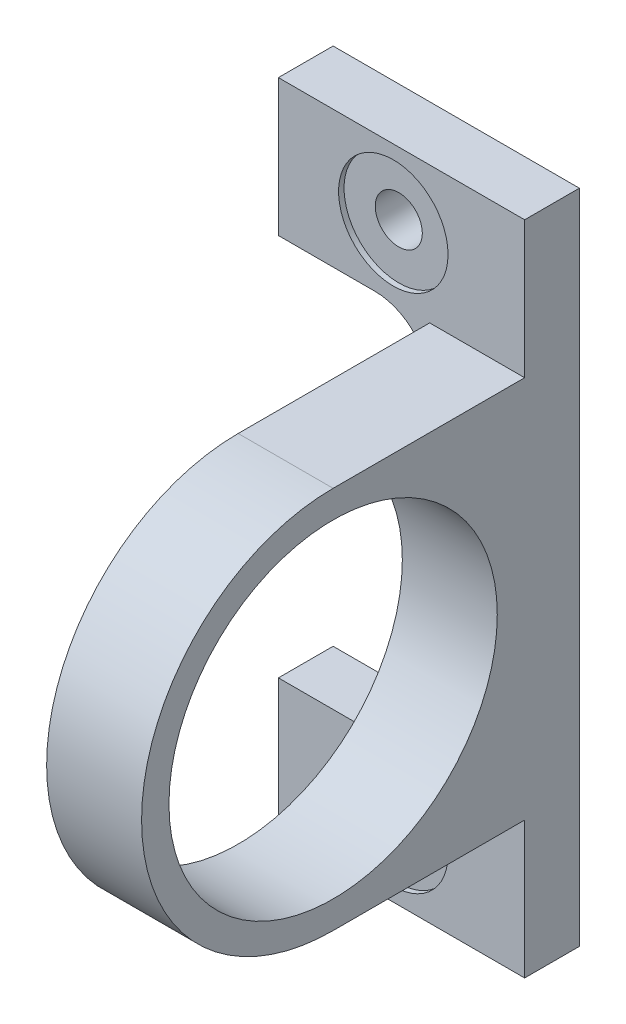
SolidWorks part; units mm, degrees
ref_plane "前视基准面" through (0, 0, 0) normal (0, 0, 1) x (1, 0, 0)
ref_plane "上视基准面" through (0, 0, 0) normal (0, 1, 0) x (1, 0, 0)
ref_plane "右视基准面" through (0, 0, 0) normal (1, 0, 0) x (0, 0, -1)
sketch "草图2" plane through (0, 0, 0) normal (0, 0, 1) x (1, 0, 0)
  line L0 (-14.7736, 24.3382) -> (-14.7736, -35.6618)
  line L1 (-14.7736, -35.6618) -> (30.2264, -35.6618)
  line L2 (7.7264, -35.6618) -> (7.7264, -23.1618)
  line L3 (21.55, -23.1618) -> (-6.0971, -23.1618)
  line L4 (-6.0971, -23.1618) -> (-6.0971, 11.8382)
  line L5 (-6.0971, 11.8382) -> (21.55, 11.8382)
  line L6 (7.7264, 11.8382) -> (7.7264, 24.3382)
  line L7 (30.2264, 24.3382) -> (-14.7736, 24.3382)
  line L8 (7.7264, 28.8603) -> (7.7264, -39.8897) construction
  line L9 (21.55, -23.1618) -> (21.55, 11.8382)
  line L10 (30.2264, 24.3382) -> (30.2264, -35.6618)
  line L11 (-18.1559, -5.6618) -> (33.2411, -5.6618) construction
  line L12 (44.0218, -5.6618) -> (44.0218, 26.2521) construction
  point P16 (-6.0971, -5.6618)
  point P17 (-14.7736, -5.6618)
  dimension "D1" = 45
  dimension "D2" = 35
  dimension "D3" = 60
extrude "凸台-拉伸2" add sketch "草图2" along normal blind 5 contours L6 L7 L0 L1 L2 L3 L4 L5 | L10 L7 L6 L5 L9 L3 L2 L1 region at (-3.5236, 23.6974, 0) region at (18.9764, 23.6974, 0)
sketch "草图4" plane through (0, 0, 5) normal (0, 0, 1) x (1, 0, 0)
  line L0 (-18.165, -5.6618) -> (33.9165, -5.6618) construction
  line L1 (-14.7736, 24.3382) -> (-14.7736, -35.6618) construction
  line L2 (-14.7736, -23.1618) -> (-6.0971, -23.1618)
  line L3 (-14.7736, -23.1618) -> (-14.7736, 11.8382)
  line L4 (-14.7736, 11.8382) -> (-6.0971, 11.8382)
  line L5 (-6.0971, -23.1618) -> (-6.0971, 11.8382)
  line L6 (-6.0971, -23.1618) -> (-6.0971, 11.8382) construction
  line L7 (7.7264, -39.813) -> (7.7264, 28.1228) construction
  line L8 (30.2264, 11.8382) -> (21.55, 11.8382)
  line L9 (21.55, -23.1618) -> (21.55, 11.8382)
  line L10 (30.2264, -23.1618) -> (21.55, -23.1618)
  line L11 (30.2264, -23.1618) -> (30.2264, 11.8382)
  point P17 (-14.7736, -5.6618)
  dimension "D1" = 35
extrude "凸台-拉伸15" add sketch "草图4" along normal blind 35
sketch "草图5" plane through (-14.7736, 0, 0) normal (-1, 0, 0) x (0, 0, 1)
  line L0 (0, -5.6618) -> (40, -5.6618)
  line L1 (0, 24.3382) -> (0, -35.6618) construction
  line L2 (40, 11.8382) -> (40, -23.1618) construction
  line L3 (22.5, 11.8382) -> (40, 11.8382)
  line L4 (40, 11.8382) -> (40, -23.1618)
  line L5 (40, -23.1618) -> (22.5, -23.1618)
  circle A0 centre (22.5, -5.6618) radius 17.5
  line M5 (5, -23.1618) -> (40, -23.1618)
  line M6 (40, -23.1618) -> (40, 11.8382)
  line M7 (40, 11.8382) -> (5, 11.8382)
  dimension "D1" = 35
extrude "切除-拉伸1" cut sketch "草图5" against normal blind 45 contours A0 M5 M6 | A0 M6 M7 region at (-14.7736, 7.9293, 36.0911) region at (-14.7736, -19.2528, 36.0911)
sketch "草图6" plane through (-14.7736, 0, 0) normal (-1, 0, 0) x (0, 0, 1)
  circle A0 centre (22.5, -5.6618) radius 15
extrude "切除-拉伸2" cut sketch "草图6" against normal blind 45
fillet "圆角1" radius 5 4 edges at (-6.0971, 11.8382, 2.5) (21.55, 11.8382, 2.5) (-6.0971, -23.1618, 2.5) (21.55, -23.1618, 2.5)
sketch "草图7" plane through (-6.0971, 0, 0) normal (1, 0, 0) x (0, 0, -1)
  circle A0 centre (-22.5, -5.6618) radius 15
  circle A1 centre (-22.5, -5.6618) radius 13
extrude "凸台-拉伸16" add sketch "草图7" against normal blind 1
sketch "草图8" plane through (21.55, 0, 0) normal (-1, 0, 0) x (0, 0, 1)
  circle A0 centre (22.5, -5.6618) radius 15
  circle A1 centre (22.5, -5.6618) radius 10
sketch "草图9" plane through (0, 0, 5) normal (0, 0, 1) x (1, 0, 0)
  line L0 (7.7264, 24.3382) -> (7.7264, -35.6618)
  line L13 (30.2264, 24.3382) -> (-14.7736, 24.3382) construction
  line L14 (-14.7736, -35.6618) -> (30.2264, -35.6618) construction
sketch "草图11" plane through (0, 0, 5) normal (0, 0, 1) x (1, 0, 0)
  line L0 (-14.7736, 18.0882) -> (30.2264, 18.0882)
  line L1 (-14.7736, 24.3382) -> (-14.7736, 11.8382) construction
  line L2 (30.2264, 24.3382) -> (30.2264, 11.8382) construction
  line L3 (7.7264, 24.3382) -> (7.7264, -35.6618) construction
  line L4 (30.2264, 24.3382) -> (-14.7736, 24.3382) construction
  line L5 (-14.7736, -35.6618) -> (30.2264, -35.6618) construction
  line L6 (7.7264, -5.6618) -> (45.6912, -5.6618) construction
  line L10 (-14.7736, -29.4118) -> (30.2264, -29.4118)
  line L11 (-14.7736, -23.1618) -> (-14.7736, -35.6618) construction
  point P4 (-2.7736, 18.0882)
  point P16 (-2.7736, -29.4118)
  point P18 (18.2264, -29.4118)
  point P25 (18.2264, 18.0882)
  dimension "D1" = 12
split "分割1" trim tools "草图9" bodies to split 111 resulting bodies 117 118
delete or keep bodies "实体-删除/保留 2" type delete bodies bodies 117
hole_wizard "打孔尺寸(%根据六角头螺)栓 全螺纹的类型1" positions "3D草图2" profile "草图13" counterbore size "M4" standard "GB"
sketch3d "3D草图2"
  point P0 (18.2264, 18.0882, 5)
  point P3 (18.2264, -29.4118, 5)
sketch "草图13" plane through (18.2264, 18.0882, 5) normal (1, 0, 0) x (0, -1, 0)
  line L0 (0, 0) -> (0, 6.2919)
  line L1 (0, 6.2919) -> (2.15, 5)
  line L2 (2.15, 5) -> (2.15, 0.5)
  line L3 (2.15, 0.5) -> (5, 0.5)
  line L4 (5, 0.5) -> (5, 0)
  line L5 (5, 0) -> (0, 0)
  line L10 (0, 6.2919) -> (-2.15, 5) construction
  line L11 (0, -6.35) -> (0, 107.95) construction
  dimension "孔直径" = 4.3
  dimension "孔深度" = 5
  dimension "柱形沉头孔直径" = 10
  dimension "柱形沉头孔深度" = 0.5
  dimension "导头角度" = 118
